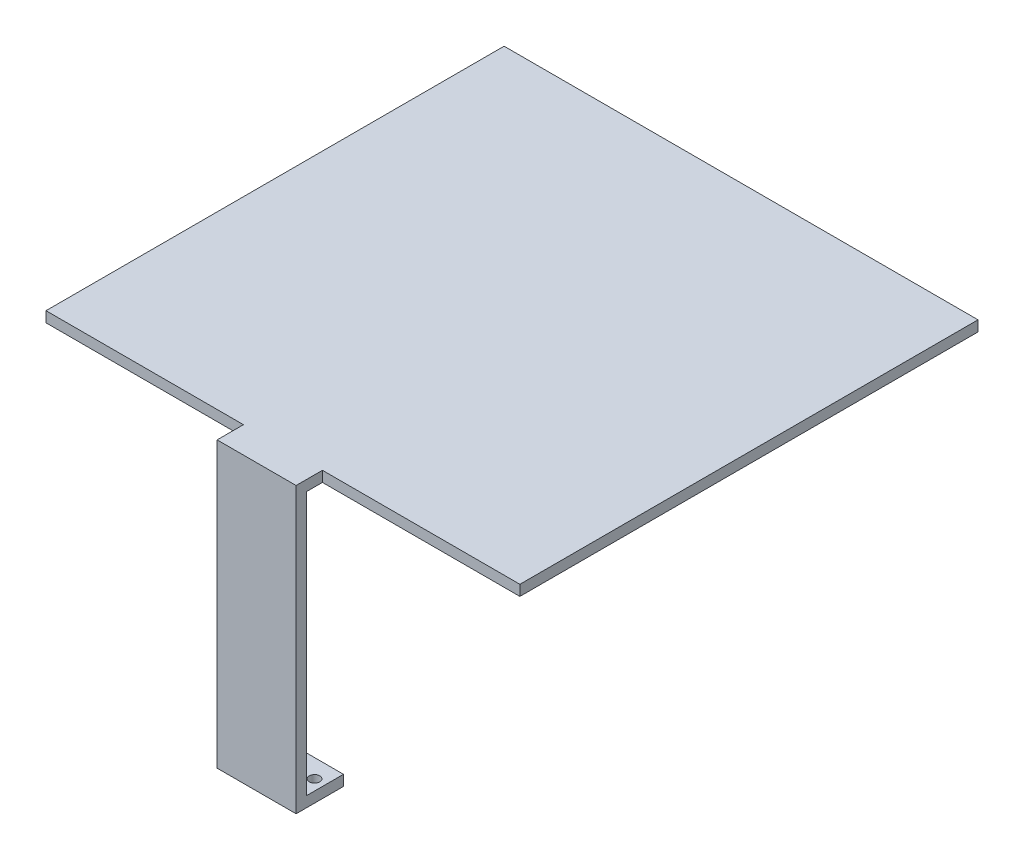
SolidWorks part; units mm, degrees
ref_plane "Front Plane" through (0, 0, 0) normal (0, 0, 1) x (1, 0, 0)
ref_plane "Top Plane" through (0, 0, 0) normal (0, 1, 0) x (1, 0, 0)
ref_plane "Right Plane" through (0, 0, 0) normal (1, 0, 0) x (0, 0, -1)
sketch "Sketch1" plane through (0, 0, 0) normal (1, 0, 0) x (0, 0, -1)
  line L0 (0, 0) -> (-7, 0)
  line L1 (-7, 0) -> (-7, 50)
  line L2 (-7, 50) -> (83, 50)
  line L3 (0, -2) -> (-9, -2)
  line L4 (-9, -2) -> (-9, 52)
  line L5 (-9, 52) -> (83, 52)
  line L6 (0, -2) -> (0, 0)
  line L7 (83, 52) -> (83, 50)
  line L8 (-4, 50) -> (-4, 52)
  point P11 (0, 0)
  point P12 (0, 0)
  dimension "D1" = 7
  dimension "D2" = 50
  dimension "D3" = 90
  dimension "D5" = 3
  dimension "D4" = 2
extrude "Boss-Extrude1" add sketch "Sketch1" along normal mid plane 15 contours L5 L7 L2 L1 L0 L6 L3 L4
extrude "Boss-Extrude2" add sketch "Sketch1<4>" along normal mid plane 90 contours L8 L2 L7 L5 region at (0, 51, -39.5)
sketch "Sketch1<4>" plane through (0, 0, 0) normal (1, 0, 0) x (0, 0, -1) same geometry as "Sketch1"
sketch "Sketch2" plane through (0, 0, 0) normal (0, 1, 0) x (1, 0, 0)
  line L0 (-7.5, 0) -> (-7.5, -7) construction
  line L1 (0, 0) -> (0, -9) construction
  line L4 (7.5, -9) -> (-7.5, -9) construction
  circle A0 centre (-5.5, -3.5) radius 1
  circle A1 centre (5.5, -3.5) radius 1
  point P5 (-7.5, -3.5)
  dimension "D2" = 2
  dimension "D1" = 5.5
extrude "Cut-Extrude1" cut sketch "Sketch2" against normal through all
